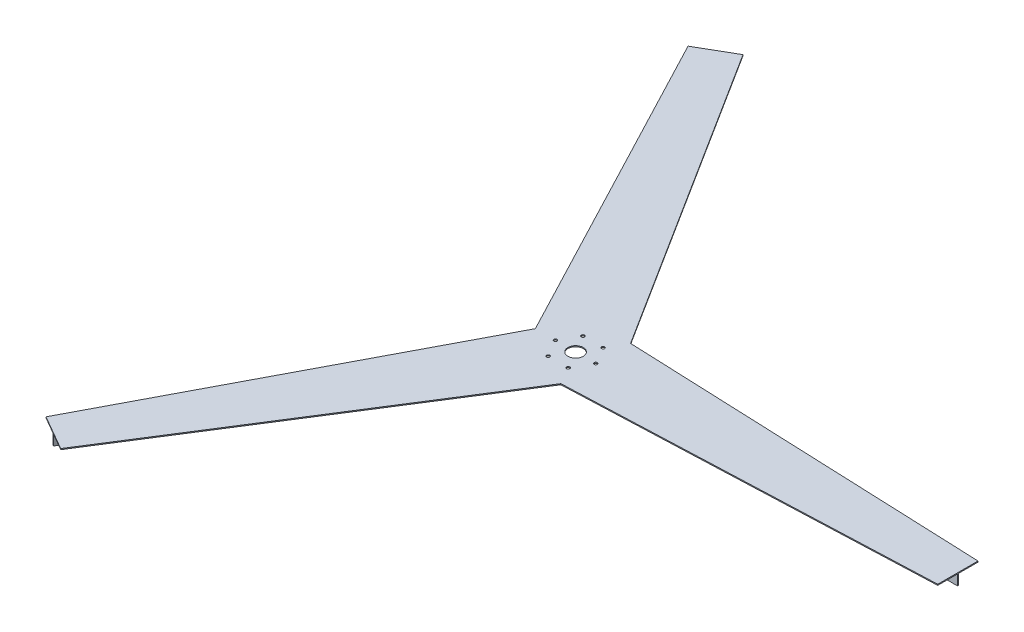
SolidWorks part; units mm, degrees
ref_plane "Alzado" through (0, 0, 0) normal (0, 0, 1) x (1, 0, 0)
ref_plane "Planta" through (0, 0, 0) normal (0, 1, 0) x (1, 0, 0)
ref_plane "Vista lateral" through (0, 0, 0) normal (1, 0, 0) x (0, 0, -1)
sketch "Croquis1" plane through (0, 0, 0) normal (0, 1, 0) x (1, 0, 0)
  line L0 (0, 0) -> (950, 0) construction
  line L1 (-431.6987, -847.7241) -> (-518.3013, -797.7241)
  line L2 (-100, 0) -> (-518.3013, -797.7241)
  line L3 (-431.6987, -847.7241) -> (50, -86.6025)
  line L6 (950, 50) -> (950, -50)
  line L9 (50, 86.6025) -> (0, 0) construction
  line L10 (0, 0) -> (-475, -822.7241) construction
  line L18 (0, 0) -> (50, -86.6025) construction
  line L19 (50, -86.6025) -> (0, 0) construction
  line L20 (0, 0) -> (9.525, 16.4978) construction
  line L22 (50, -86.6025) -> (950, -50)
  line L25 (950, 50) -> (50, 86.6025)
  line L27 (0, 0) -> (-100, 0) construction
  line L28 (-518.3013, 797.7241) -> (-431.6987, 847.7241)
  line L29 (50, 86.6025) -> (-431.6987, 847.7241)
  line L30 (-518.3013, 797.7241) -> (-100, 0)
  line L31 (0, 0) -> (-475, 822.7241) construction
  line L32 (-100, 0) -> (0, 0) construction
  line L33 (0, 0) -> (50, 86.6025) construction
  line L34 (50, 86.6025) -> (50, -86.6025) construction
  circle A0 centre (0, 0) radius 19.05
  point P3 (475, 0)
  point P8 (-237.5, -411.3621)
  point P17 (-237.5, 411.3621)
  point P23 (0, 0)
  point P26 (0, 0)
  dimension "D2" = 38.1
  dimension "D3" = 3
  dimension "D4" = 950
  dimension "D6" = 100
  dimension "D9" = 60
  dimension "D12" = 100
extrude "Saliente-Extruir3" add sketch "Croquis1" along normal blind 2.5 contours L25 L28 L22 L6 A0 region at (-463.7857, 0, 803.3003)
sketch "Croquis2" plane through (0, 0, 0) normal (0, -1, 0) x (1, 0, 0)
  line L0 (950, 0) -> (65, 0) construction
  line L1 (950, -50) -> (950, 50) construction
  line L2 (65, 1.25) -> (65, -1.25)
  line L3 (65, -1.25) -> (950, -1.25)
  line L4 (950, -1.25) -> (950, 1.25)
  line L5 (950, 1.25) -> (65, 1.25)
  line L18 (-473.9175, -823.3491) -> (-31.4175, -56.9167)
  line L22 (-33.5825, -55.6667) -> (-476.0825, -822.0991)
  line L23 (-476.0825, -822.0991) -> (-473.9175, -823.3491)
  line L24 (-475, -822.7241) -> (-32.5, -56.2917) construction
  line L25 (-31.4175, -56.9167) -> (-33.5825, -55.6667)
  line L26 (-476.0825, 822.0991) -> (-33.5825, 55.6667)
  line L27 (-31.4175, 56.9167) -> (-473.9175, 823.3491)
  line L28 (-473.9175, 823.3491) -> (-476.0825, 822.0991)
  line L29 (-475, 822.7241) -> (-32.5, 56.2917) construction
  line L30 (-33.5825, 55.6667) -> (-31.4175, 56.9167)
  point P8 (65, 0)
  point P21 (5, 2.8868)
  point P26 (0, 0)
  dimension "D1" = 885
  dimension "D2" = 2.5
  dimension "D3" = 3
extrude "Saliente-Extruir4" add sketch "Croquis2" along normal blind 25.4
sketch "Croquis4" plane through (0, 2.5, 0) normal (0, 1, 0) x (1, 0, 0)
  line L0 (0, 0) -> (50, 0) construction
  line L1 (50, 0) -> (25, 43.3013) construction
  line L2 (25, 43.3013) -> (-25, 43.3013) construction
  line L3 (-25, 43.3013) -> (-50, 0) construction
  line L4 (-50, 0) -> (-25, -43.3013) construction
  line L5 (-25, -43.3013) -> (25, -43.3013) construction
  line L6 (25, -43.3013) -> (50, 0) construction
  circle A2 centre (0, 0) radius 43.3013 construction
  circle A3 centre (25, -43.3013) radius 4
  circle A4 centre (-25, -43.3013) radius 4
  circle A5 centre (-50, 0) radius 4
  circle A6 centre (-25, 43.3013) radius 4
  circle A7 centre (25, 43.3013) radius 4
  circle A8 centre (50, 0) radius 4
  point P26 (0, 0)
  dimension "D4" = 8
  dimension "D5" = 50
  dimension "D6" = 86.6025
  dimension "D2" = 50
  dimension "D7" = 50
  dimension "D8" = 6
extrude "Cortar-Extruir1" cut sketch "Croquis4" against normal blind 2.54
